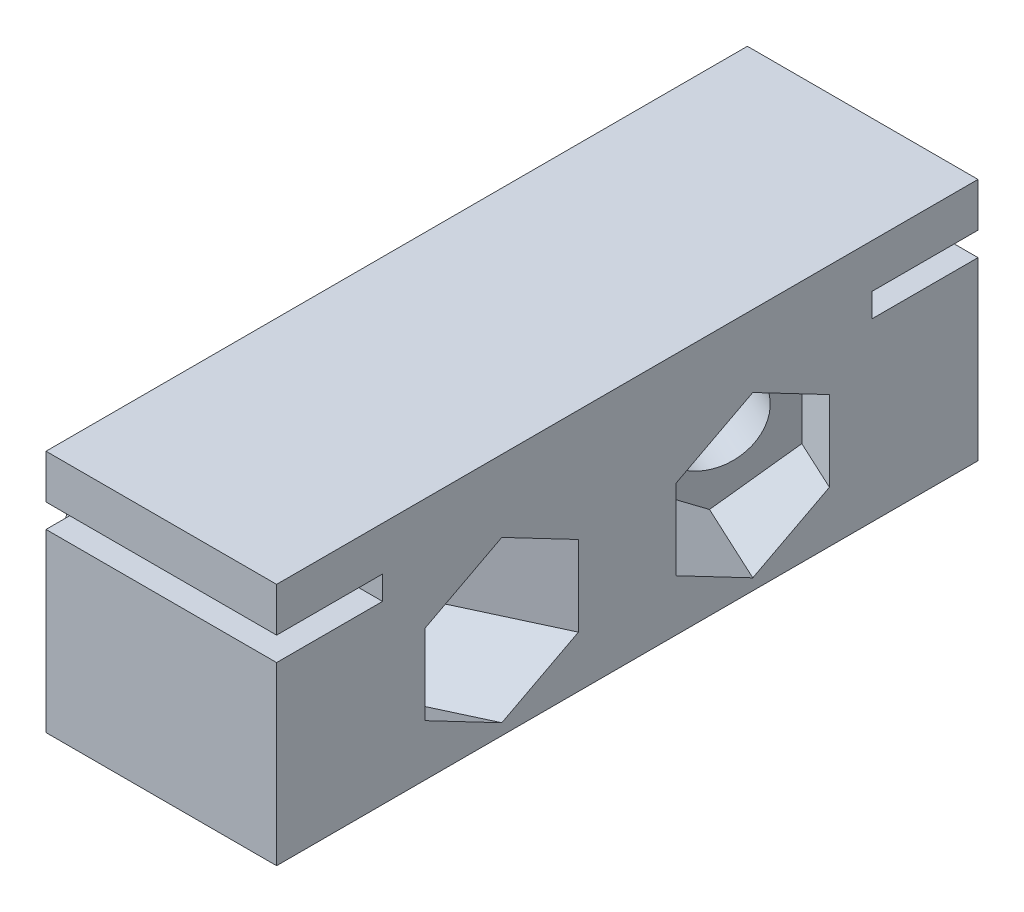
SolidWorks part; units mm, degrees
ref_plane "Front Plane" through (0, 0, 0) normal (0, 0, 1) x (1, 0, 0)
ref_plane "Top Plane" through (0, 0, 0) normal (0, 1, 0) x (1, 0, 0)
ref_plane "Right Plane" through (0, 0, 0) normal (1, 0, 0) x (0, 0, -1)
sketch "Sketch3" plane through (0, 0, 0) normal (0, 0, 1) x (1, 0, 0)
  line L0 (0, -1086.5497) -> (0, 53240.9333) construction
  line L1 (-1086.5497, 0) -> (53240.9333, 0) construction
  line L2 (-44.1325, 4.0322) -> (-23.8125, 4.0322)
  line L3 (-23.8125, 4.0322) -> (-23.8125, -13.5572)
  line L4 (-23.8125, -13.5572) -> (-44.1325, -13.5572)
  line L5 (-44.1325, -13.5572) -> (-44.1325, -0.8572)
  line L6 (-44.1325, -0.8572) -> (-30.7975, -0.8572)
  line L7 (-30.7975, -0.8572) -> (-30.7975, 0.8573)
  line L8 (-30.7975, 0.8573) -> (-44.1325, 0.8572)
  line L9 (-44.1325, 0.8572) -> (-44.1325, 4.0322)
  point P4 (-30.7975, 0)
  dimension "D1" = 1.7145
  dimension "D2" = 12.7
  dimension "D3" = 3.175
  dimension "D4" = 6.985
  dimension "D5" = 47.625
  dimension "D6" = 20.32
revolve "Revolve1" add sketch "Sketch3" angle 70 mid plane about L0
sketch "Sketch4" [suppressed] plane through (0, 3.81, 0) normal (0, 1, 0) x (1, 0, 0)
  line L8 (-14.6879, 43.8645) -> (0, 0)
  line L9 (0, 0) -> (1.2005, 46.2427)
  arc A4 (-14.6879, 43.8645) -> (1.2005, 46.2427) centre (0, 0) cw
  circle A5 centre (0, 0) radius 46.2583 construction
  dimension "D1" = 20
extrude "Cut-Extrude1" [suppressed] cut sketch "Sketch4" against normal through all
sketch "Sketch10" plane through (0, 4.0323, 0) normal (0, 1, 0) x (1, 0, 0)
  line L0 (-19.5061, 13.6583) -> (-19.5061, -13.6583)
  arc A0 (-19.5061, 13.6583) -> (-19.5061, -13.6583) centre (0, 0) ccw
extrude "Boss-Extrude1" add sketch "Sketch10" against normal up to surface (17.5895 mm away) up to face at (-30.9006, -13.5572, 0)
pattern_circular "CirPattern4" [suppressed] count 4 over 360 of bodies 101
sketch "Sketch6" plane through (0, 0, 0) normal (0.5736, 0, 0.8192) x (0.8192, 0, -0.5736)
  line L0 (-29.1465, -11.9697) -> (-29.1465, -2.7305)
  line L1 (-23.8125, -13.5572) -> (-23.8125, 4.0323) construction
  line L2 (-29.1465, -2.7305) -> (-25.4635, -2.7305)
  line L3 (-25.4635, -2.7305) -> (-25.4635, -11.9697)
  line L4 (-25.4635, -11.9697) -> (-29.1465, -11.9697)
  line L6 (-44.1325, -13.5572) -> (-23.8125, -13.5572) construction
  dimension "D1" = 9.2393
  dimension "D2" = 3.683
  dimension "D3" = 1.651
  dimension "D4" = 1.5875
extrude "Cut-Extrude2" [suppressed] cut sketch "Sketch6" against normal blind 8.89
sketch "Sketch7" plane through (0, 0, 0) normal (0.5736, 0, -0.8192) x (-0.8192, 0, -0.5736)
  line L0 (44.1325, -13.5572) -> (23.8125, -13.5572) construction
  line L1 (25.527, -2.818) -> (29.21, -2.818)
  line L2 (25.527, -2.818) -> (25.527, -12.0572)
  line L3 (25.527, -12.0572) -> (29.21, -12.0572)
  line L4 (29.21, -2.818) -> (29.21, -12.0572)
  line L6 (23.8125, -13.5572) -> (23.8125, 4.0323) construction
  dimension "D1" = 3.683
  dimension "D2" = 9.2393
  dimension "D3" = 1.5
  dimension "D4" = 1.7145
extrude "Cut-Extrude3" [suppressed] cut sketch "Sketch7" against normal blind 8.89
sketch "Sketch8" [suppressed] plane through (-23.8754, 0, 16.7177) normal (0.8192, 0, -0.5736) x (-0.5736, 0, -0.8192)
  line L0 (-973.4151, -2.818) -> (49026.5849, -2.818) construction
  line L1 (23.9875, -12.0572) -> (27.4484, -12.0572) construction
  line L2 (-973.2795, -12.0572) -> (49026.7205, -12.0572) construction
  line L3 (8.89, -12.0572) -> (0, -12.0572) construction
  line L4 (0, -1007.1908) -> (0, 48992.8092) construction
  line L5 (8.89, -12.0572) -> (8.89, -2.818) construction
  line L6 (8.89, -1008.035) -> (8.89, 48991.965) construction
  line L7 (8.89, -2.818) -> (0, -2.818) construction
  line L8 (0, -12.0572) -> (0, -2.818) construction
  line L9 (8.89, -12.0572) -> (0, -2.818) construction
  line L10 (8.89, -2.818) -> (0, -12.0572) construction
  line L11 (24.4079, -2.818) -> (20.947, -2.818) construction
  circle A1 centre (4.445, -7.4376) radius 3.302
  point P7 (4.445, -7.4376)
  dimension "D2" = 6.604
  dimension "D1" = 8.89
extrude "Cut-Extrude4" [suppressed] cut sketch "Sketch8" against normal through all both and the other way through all
sketch "Sketch9" [suppressed] plane through (-23.9274, 0, -16.7542) normal (0.8192, 0, 0.5736) x (0.5736, 0, -0.8192)
  line L0 (-1025.1564, -2.7305) -> (48974.8436, -2.7305) construction
  line L1 (0, -13.5572) -> (0, 4.0323) construction
  line L2 (-1024.9864, -11.9697) -> (48975.0136, -11.9697) construction
  line L3 (0, -11.9697) -> (-8.89, -11.9697) construction
  line L4 (-23.9279, -2.7305) -> (-27.3888, -2.7305) construction
  line L5 (-24.3482, -11.9697) -> (-27.3888, -11.9697) construction
  line L6 (-8.89, -1006.6284) -> (-8.89, 48993.3716) construction
  line L7 (-8.89, -12.0573) -> (-8.89, -2.818) construction
  line L8 (0, -1006.7588) -> (0, 48993.2412) construction
  line L10 (0, -11.9697) -> (0, -2.7305) construction
  line L11 (0, -2.7305) -> (-8.89, -2.7305) construction
  line L12 (-8.89, -11.9697) -> (-8.89, -2.7305) construction
  line L13 (0, -11.9697) -> (-8.89, -2.7305) construction
  line L14 (0, -2.7305) -> (-8.89, -11.9697) construction
  circle A0 centre (-4.445, -7.3501) radius 3.302
  point P16 (-4.445, -7.3501)
  dimension "D1" = 6.604
extrude "Cut-Extrude5" [suppressed] cut sketch "Sketch9" against normal through all both and the other way through all
sketch "Sketch11" plane through (0, 4.0323, 0) normal (0, 1, 0) x (1, 0, 0)
  line L0 (-19.5061, 7.5282) -> (-19.5061, 50007.5282) construction
  line L10 (-19.5061, -13.6583) -> (-19.5061, 13.6583) construction
  line L11 (-36.1512, 25.3134) -> (-19.5061, 25.3134)
  line L12 (-19.5061, 25.3134) -> (-19.5061, 13.6583)
  line L13 (-19.5061, 13.6583) -> (-36.1512, 25.3134)
  line L14 (-36.1512, -25.3134) -> (-19.5061, -25.3134)
  line L15 (-19.5061, -25.3134) -> (-19.5061, -13.6583)
  line L16 (-19.5061, -13.6583) -> (-36.1512, -25.3134)
extrude "Boss-Extrude2" add sketch "Sketch11" against normal up to surface (3.175 mm away) up to face at (-34.0773, 0.8573, 0)
sketch "Sketch12" plane through (0, -13.5572, 0) normal (0, -1, 0) x (1, 0, 0)
  line L0 (-36.1512, 25.3134) -> (-19.5061, 25.3134)
  line L1 (-19.5061, 25.3134) -> (-19.5061, 13.6583)
  line L2 (-19.5061, 13.6583) -> (-36.1512, 25.3134)
  line L3 (-36.1512, -25.3134) -> (-19.5061, -13.6583)
  line L4 (-19.5061, -13.6583) -> (-19.5061, -25.3134)
  line L5 (-19.5061, -25.3134) -> (-36.1512, -25.3134)
extrude "Boss-Extrude3" add sketch "Sketch12" against normal up to surface (12.7 mm away) up to face at (-34.0773, -0.8572, 0)
ref_axis "Axis1" through (0, 4.0323, 0) along (0, -1, 0)
ref_plane "Plane5" [suppressed] through (0, -6.9532, 0) normal (0, -1, 0) x (-1, 0, 0)
ref_axis "Axis2" [suppressed] through (-19.5061, -6.9532, 25.3134) along (0, 0, -1)
ref_plane "Plane1" through (0, -6.9532, 0) normal (0, -1, 0) x (-1, 0, 0)
sketch "Sketch14" plane through (0, -6.9532, 0) normal (0, -1, 0) x (-1, 0, 0)
  line L0 (8.6226, 6.7607) -> (10.7286, 2.2258) construction
  line L1 (8.6226, 6.7607) -> (41.0504, 21.8198) construction
  line L2 (41.0504, 21.8198) -> (43.1563, 17.2849) construction
  line L3 (43.1563, 17.2849) -> (10.7286, 2.2258) construction
  line L4 (9.6756, 4.4932) -> (40.027, 18.5881)
  circle A0 centre (0, 0) radius 10.668 construction
  arc A1 (36.1512, -25.3134) -> (36.1512, 25.3134) centre (0, 0) ccw construction
  point P5 (9.6756, 4.4932)
  dimension "D1" = 21.336
  dimension "D2" = 5
sweep "Cut-Sweep1" cut path "Sketch14" circular profile diameter 6.604 parameters "D3"=6.604
mirror "Mirror1" about plane through (0, 0, 0) normal (0, 0, 1) of "Cut-Sweep1"
ref_plane "Plane3" through (0, 0, 0) normal (-0.907, 0, -0.4212) x (-0.4212, 0, 0.907)
sketch "Sketch37" plane through (0, 0, 0) normal (-0.907, 0, -0.4212) x (-0.4212, 0, 0.907)
  line L7 (-5.0165, -4.057) -> (-5.0165, -9.8495)
  line L8 (-5.0165, -9.8495) -> (0, -12.7458)
  line L9 (0, -12.7458) -> (5.0165, -9.8495)
  line L10 (5.0165, -9.8495) -> (5.0165, -4.057)
  line L11 (5.0165, -4.057) -> (0, -1.1607)
  line L12 (0, -1.1607) -> (-5.0165, -4.057)
  circle A1 centre (0, -6.9532) radius 5.0165 construction
  point P9 (0, -6.9532)
  dimension "D1" = 10.033
extrude "Cut-Extrude7" cut sketch "Sketch37" along normal blind 27.94
mirror "Mirror2" about plane through (0, 0, 0) normal (0, 0, 1) of "Cut-Extrude7"
sketch "Sketch38" plane through (0, -0.8572, 0) normal (0, 1, 0) x (1, 0, 0)
  line L0 (-25.2278, 17.6647) -> (-19.5061, 17.6647)
  line L1 (-19.5061, 25.3134) -> (-19.5061, 13.6583) construction
  line L2 (-19.5061, 17.6647) -> (-19.5061, 13.6583)
  line L3 (-19.5061, 13.6583) -> (-25.2278, 17.6647) construction
  line L4 (-19.5061, 13.6583) -> (-25.2278, 17.6647)
  line L5 (-25.2278, -17.6647) -> (-19.5061, -13.6583)
  line L6 (-19.5061, -13.6583) -> (-19.5061, -17.6647)
  line L7 (-19.5061, -13.6583) -> (-19.5061, -25.3134) construction
  line L8 (-19.5061, -17.6647) -> (-25.2278, -17.6647)
extrude "Boss-Extrude4" add sketch "Sketch38" along normal up to surface (1.7145 mm away)
sketch "Sketch39" plane through (0, 0.8573, 0) normal (0, -1, 0) x (1, 0, 0)
  line L0 (-25.2278, -17.6647) -> (-25.2278, 17.6647)
  arc A0 (-25.2278, -17.6647) -> (-25.2278, 17.6647) centre (0, 0) cw
  arc A1 (-25.2278, 17.6647) -> (-25.2278, -17.6647) centre (0, 0) ccw construction
extrude "Cut-Extrude8" cut sketch "Sketch39" along normal up to surface (1.7145 mm away)
sketch "Sketch44" plane through (0, -13.5572, 0) normal (0, -1, 0) x (1, 0, 0)
  line L0 (-36.1512, 25.3134) -> (-36.1512, -25.3134)
  arc A0 (-36.1512, 25.3134) -> (-36.1512, -25.3134) centre (0, 0) ccw
extrude "Cut-Extrude9" cut sketch "Sketch44" against normal through all
ref_plane "Plane6" through (-39.9068, 0, -18.5323) normal (-0.907, 0, -0.4212) x (-0.4212, 0, 0.907)
sketch "Sketch45" plane through (-39.9068, 0, -18.5323) normal (-0.907, 0, -0.4212) x (-0.4212, 0, 0.907)
  circle A0 centre (0, -6.9532) radius 3.302
  circle A1 centre (0, -6.9532) radius 5
  circle A2 centre (0, -6.9532) radius 3.302 construction
  dimension "D1" = 10
extrude "Boss-Extrude5" add sketch "Sketch45" against normal up to surface (5.6742 mm away) up to face at (-36.1512, -6.9532, 20.4289)
mirror "Mirror3" about plane through (0, 0, 0) normal (0, 0, 1) of "Boss-Extrude5"
